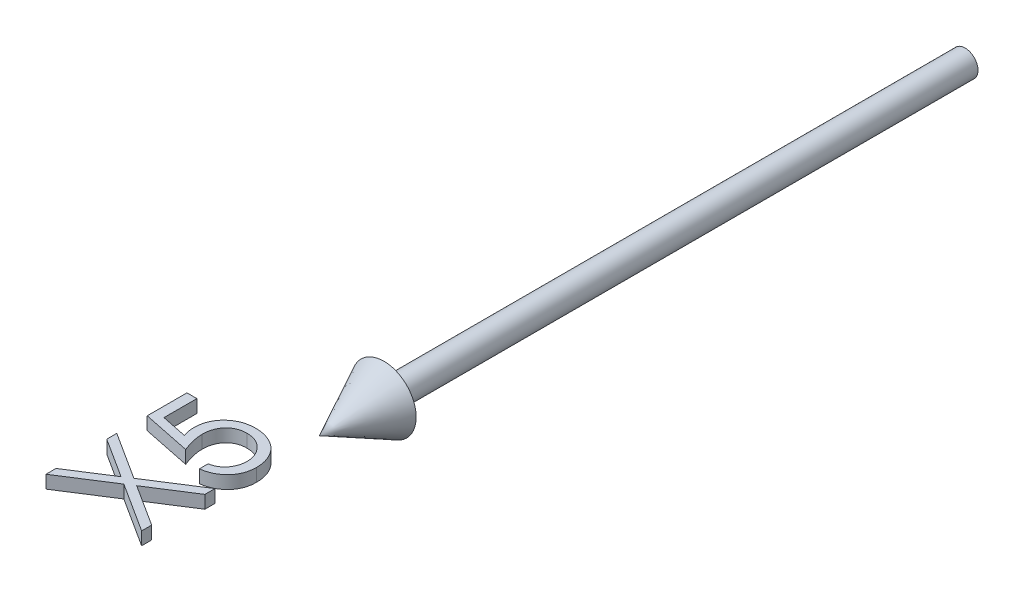
SolidWorks part; units mm, degrees
ref_plane "Front Plane" through (0, 0, 0) normal (0, 0, 1) x (1, 0, 0)
ref_plane "Top Plane" through (0, 0, 0) normal (0, 1, 0) x (1, 0, 0)
ref_plane "Right Plane" through (0, 0, 0) normal (1, 0, 0) x (0, 0, -1)
sketch "Sketch2" plane through (0, 0, 0) normal (0, 1, 0) x (1, 0, 0)
  line L0 (0, 41.95) -> (0, -114.4521) construction
  line L1 (-36.8894, 0) -> (41.4965, 0) construction
  line L2 (0, -100) -> (5, -90)
  line L3 (5, -90) -> (2, -90)
  line L4 (2, -90) -> (2, 0)
  line L5 (2, 0) -> (0, 0)
  line L6 (0, 0) -> (0, -100)
  dimension "D1" = 100
  dimension "D2" = 2
  dimension "D3" = 10
  dimension "D4" = 5
revolve "Revolve1" add sketch "Sketch2" angle 360 about L0
sketch "Sketch3" plane through (0, 0, 0) normal (0, 1, 0) x (1, 0, 0)
  line L0 (0, -103.9528) -> (0, -147.2622) construction
  line L1 (-18.6107, -118.3811) -> (18.3141, -118.3811) construction
  text T0 "X5\r\n\r\n" font "Century Gothic" height 15
extrude "Boss-Extrude1" add sketch "Sketch3" against normal blind 1 and the other way blind 1 separate body
equation "\"frame_arrow_length\"=100"
equation "\"D1@Sketch2\"=\"frame_arrow_length\""
equation "\"frame_arrow_odA\"=4"
equation "\"D2@Sketch2\"=\"frame_arrow_odA\"/2"
equation "\"frame_arrow_head_od\"=5"
equation "\"D4@Sketch2\"=\"frame_arrow_head_od\""
equation "\"frame_arrow_head_length\"=10"
equation "\"D3@Sketch2\"=\"frame_arrow_head_length\""
equation "\"tvarobot_theta1\"=30"
equation "\"link0_ringA_odA\"= 40"
equation "\"link0_ringA_odB\"= 25"
equation "\"link0_ringA_id\"= 20"
equation "\"link0_ringA_thickness\"= (\"link0_ringA_odB\" - \"link0_ringA_id\")/2"
equation "\"link0_ringA_height\"= 3"
equation "\"link0_ringA_heightA\"= 1.5"
equation "\"link0_ringA_heightB\"=\"link0_ringA_height\"-\"link0_ringA_heightA\""
equation "\"link0_ringB_odA\"= 40"
equation "\"link0_ringB_odB\"= 29"
equation "\"link0_ringB_id\"= \"link0_shaftA_bearing_id\"+1"
equation "\"link0_ringB_thickness\"= (\"link0_ringB_odB\" - \"link0_ringB_id\")/2"
equation "\"link0_ringB_height\"= 3"
equation "\"link0_ringB_heightA\"= 1.5"
equation "\"link0_ringB_heightB\"=\"link0_ringB_height\"-\"link0_ringB_heightA\""
equation "\"link0_shaftA_bearing_od\"=27"
equation "\"link0_shaftA_bearing_id\"=20"
equation "\"link0_shaftA_thrust_bearing_od\"=35"
equation "\"link0_shaftA_thrust_bearing_id\"=20.04"
equation "\"link0_shaftA_retaining_ring_id\"=18.5"
equation "\"link0_shaftA_retaining_ring_groove_width\"=1.5"
equation "\"link0_shaftA_spline_length\"=8.0"
equation "\"link0_shaftA_spline_depth\"=1.0"
equation "\"link0_shaftA_spline_width\"=4.0"
equation "\"link0_shaftA_odA\"=\"link0_shaftA_bearing_id\""
equation "\"link0_shaftA_odB\"=35"
equation "\"link0_shaftA_odC\"=\"link0_shaftA_bearing_id\""
equation "\"link0_shaftA_odD\"=\"link0_shaftA_odC\"-2*\"link0_shaftA_spline_depth\""
equation "\"link0_shaftA_odE\"=\"link0_shaftA_bearing_id\""
equation "\"link0_shaftA_odF\"=\"link0_shaftA_odE\"-2*\"link0_shaftA_spline_depth\""
equation "\"link0_shaftA_idA\"=10"
equation "\"link0_shaftA_idB\"=6"
equation "\"link0_shaftA_length\"=39.5"
equation "\"link0_shaftA_lengthA\"=8.0"
equation "\"link0_shaftA_lengthB\"=12.0"
equation "\"link0_shaftA_lengthC\"=35.0"
equation "\"link0_shaftA_lengthD\"=39.0"
equation "\"link0_shaftA_lengthE\"=\"link0_shaftA_length\"-\"link0_shaftA_lengthD\""
equation "\"link0_shaftA_offsetX\"=11"
equation "\"link0_shaftA_offsetY\"=0"
equation "\"link0_shaftA_bolt_pattern_dia\"=14"
equation "\"link0_motor_center_dist\"=26"
equation "\"link0_46t_pulley_spline_length\"=8"
equation "\"link0_46t_pulley_spline_depth\"=\"link0_shaftA_spline_depth\"*1.025"
equation "\"link0_46t_pulley_spline_width\"=\"link0_shaftA_spline_width\"*1.05"
equation "\"link0_46t_pulley_idA\"=\"link0_shaftA_bearing_id\"*1.025"
equation "\"link0_46t_pulley_idB\"=\"link0_46t_pulley_idA\"-2*\"link0_46t_pulley_spline_depth\""
equation "\"link0_shaftB_spline_length\"=10"
equation "\"link0_shaftB_spline_depth\"=1.0"
equation "\"link0_shaftB_spline_width\"=1.25"
equation "\"link0_shaftB_length\"=7"
equation "\"link0_shaftB_lengthA\"=1.5"
equation "\"link0_shaftB_lengthB\"=2.75"
equation "\"link0_shaftB_odA\"=32"
equation "\"link0_shaftB_odB\"=22"
equation "\"link0_shaftB_odC\"=20"
equation "\"link0_shaftB_idA\"=10"
equation "\"link0_shaftB_bolt_diameter\"=19"
equation "\"link0_shaftB_bearing_od\"=27"
equation "\"link0_shaftB_bearing_id\"=20"
equation "\"link0_motor_length\"=46.5"
equation "\"link0_motor_width\"=28.5"
equation "\"link0_motor_height\"=34"
equation "\"link0_motor_offset\"=8"
equation "\"link0_shellA_thickness\"=2.5"
equation "\"link0_shellB_thickness\"=\"link0_shellA_thickness\""
equation "\"link0_plateA_shellA_height\"=48"
equation "\"link0_shellA_width\" =\"link0_plateA_width\""
equation "\"link0_shellA_height\" = \"link0_plateA_shellA_height\"-\"link0_plateA_height\""
equation "\"link0_shellA_length\" = \"link0_plateA_lengthB\" "
equation "\"link0_shellB_length\"=\"link0_shellA_length\""
equation "\"link0_shellA_radius\" = 0.375*25.4"
equation "\"link0_shellA_radiusA\"= \"link0_plateA_radiusA\""
equation "\"link0_shellA_radiusB\"= \"link0_plateA_radiusB\""
equation "\"link0_shellA_radiusC\"= 3"
equation "\"link0_postA_height\"=7"
equation "\"link0_postA_width\"=16"
equation "\"link0_postA_length\"=20"
equation "\"link0_postA_posX\"=22"
equation "\"link0_postA_posY\"=17.5"
equation "\"link0_postA_pocket_width\"=6.0"
equation "\"link0_postA_pocket_length\"=2.5"
equation "\"link0_postA_pocket_depth\"=9"
equation "\"link0_postA_pocket_posZ\"=10"
equation "\"link0_postB_height\"=7"
equation "\"link0_postB_width\"=16"
equation "\"link0_postB_length\"=20"
equation "\"link0_postB_posX\"=22"
equation "\"link0_postB_posY\"=17.5"
equation "\"link0_postB_id\"=3.0"
equation "\"link0_postB_pocket_width\"=6.0"
equation "\"link0_postB_pocket_length\"=2.5"
equation "\"link0_postB_pocket_depth\"=9"
equation "\"link0_postB_pocket_posZ\"=10"
equation "\"link0_postC_height\"=7"
equation "\"link0_postC_width\"=16"
equation "\"link0_postC_length\"=20"
equation "\"link0_postC_posX\"=22"
equation "\"link0_postC_posY\"=17.5"
equation "\"link0_postC_id\"=3.0"
equation "\"link0_postC_pocket_width\"=6.0"
equation "\"link0_postC_pocket_length\"=2.5"
equation "\"link0_postC_pocket_depth\"=9"
equation "\"link0_postC_pocket_posZ\"=10"
equation "\"link0_postD_height\"=7"
equation "\"link0_postD_width\"=16"
equation "\"link0_postD_length\"=20"
equation "\"link0_postD_posX\"=22"
equation "\"link0_postD_posY\"=17.5"
equation "\"link0_postD_id\"=3.0"
equation "\"link0_postD_pocket_width\"=6.0"
equation "\"link0_postD_pocket_length\"=3.0"
equation "\"link0_postD_pocket_depth\"=9"
equation "\"link0_postD_pocket_posZ\"=10"
equation "\"link0_postE_height\"=5"
equation "\"link0_postE_width\"=16"
equation "\"link0_postE_length\"=\"link0_plateE_lengthA\"-\"link0_lip_height\""
equation "\"link0_postE_posZ\"=22"
equation "\"link0_postE_posX\"=17.5"
equation "\"link0_postE_posY\"=22"
equation "\"link0_postE_id\"=3.0"
equation "\"link0_postE_cbore_id\"=6.5"
equation "\"link0_postE_hole_id\"=3"
equation "\"link0_postF_posZ\"=22"
equation "\"link0_postF_posX\"=17.5"
equation "\"link0_postF_posY\"=\"link0_plateB_lengthA\"+4"
equation "\"link0_postF_id\"=3.0"
equation "\"link0_postF_cbore_id\"=6.5"
equation "\"link0_postF_hole_id\"=3"
equation "\"link0_postG_posZ\"=22"
equation "\"link0_postG_posX\"=17.5"
equation "\"link0_postG_posY\"=\"link0_plateB_lengthA\"+12"
equation "\"link0_postG_id\"=3.0"
equation "\"link0_postG_cbore_id\"=6.5"
equation "\"link0_postG_hole_id\"=3"
equation "\"link0_postHIJ_posY\"=6"
equation "\"link0_postH_posX\"=28"
equation "\"link0_postH_posY\"=20"
equation "\"link0_postH_posZ\"=20"
equation "\"link0_postH_length\"=10"
equation "\"link0_postI_posX\"=28"
equation "\"link0_postI_posY\"=20"
equation "\"link0_postI_posZ\"=135"
equation "\"link0_postI_length\"=10"
equation "\"link0_postJ_posX\"=28"
equation "\"link0_postJ_posY\"=20"
equation "\"link0_postJ_posZ\"=175"
equation "\"link0_postJ_length\"=10"
equation "\"link0_postK_posX\"=28"
equation "\"link0_postK_posY\"=20"
equation "\"link0_postK_posZ\"=175"
equation "\"link0_postK_length\"=10"
equation "\"link0_postL_posX\"=28"
equation "\"link0_postL_posY\"=20"
equation "\"link0_postL_posZ\"=135"
equation "\"link0_postL_length\"=10"
equation "\"link0_postM_posX\"=28"
equation "\"link0_postM_posY\"=20"
equation "\"link0_postM_posZ\"=35"
equation "\"link0_postM_length\"=10"
equation "\"link0_plateA_lengthA\"=30"
equation "\"link0_plateA_lengthB\"=150"
equation "\"link0_plateA_lengthC\"=30"
equation "\"link0_plateA_length\"=\"link0_plateA_lengthA\"+\"link0_plateA_lengthB\"+\"link0_plateA_lengthC\""
equation "\"link0_plateA_width\"=  68"
equation "\"link0_plateA_height\"= \"link0_plateA_radiusA\""
equation "\"link0_plateA_thickness\"=\"link0_shellA_thickness\""
equation "\"link0_plateA_radius\"= 9.5"
equation "\"link0_plateA_radiusA\"= 18"
equation "\"link0_plateA_radiusB\"= 18"
equation "\"link0_plateA_radiusC\"= 3"
equation "\"link0_plateB_length\"= 40"
equation "\"link0_plateB_width\"= \"link0_plateA_width\"*1.005"
equation "\"link0_plateB_height\"= \"link0_plateA_shellA_height\"*1.005"
equation "\"link0_plateB_lengthA\"=\"link0_lip_height\"+\"link0_plateD_thickness\"+\"link0_motor_mount_thickness\""
equation "\"link0_plateB_lengthB\"=\"link0_plateB_height\"-\"link0_plateB_lengthA\""
equation "\"link0_plateB_radiusA\"= \"link0_plateA_radiusA\""
equation "\"link0_plateB_radiusB\"= \"link0_plateA_radiusB\""
equation "\"link0_plateB_radiusC\"= 3"
equation "\"link0_plateB_idA\"=\"link0_shaftA_odC\"+1"
equation "\"link0_plateB_idB\"=\"link0_shaftA_bearing_od\"-2"
equation "\"link0_plateB_idC\"=\"link0_shaftA_bearing_od\"*1.005"
equation "\"link0_plateB_idD\"=\"link0_shaftA_thrust_bearing_od\"+1 "
equation "\"link0_plateB_depthA\"=1.0"
equation "\"link0_plateB_depthB\"=2.0"
equation "\"link0_plateB_depthC\"=8"
equation "\"link0_plateB_depthD\"=\"link0_plateB_length\"-\"link0_lip_height\"-\"link0_plateD_thickness\" "
equation "\"link0_plateC_length\"=\"link0_plateB_length\""
equation "\"link0_plateC_width\"= \"link0_plateB_width\""
equation "\"link0_plateC_height\"= .1*25.4"
equation "\"link0_plateA_hole_od\" = 0.1*25.4"
equation "\"link0_plateA_hole_delx\" = 0.5*25.4"
equation "\"link0_plateA_hole_delz\" = 0.75*25.4"
equation "\"link0_plateA_hole_offx\" = 0.0*25.4"
equation "\"link0_plateA_hole_offz\" = \"link0_plateA_length\"/2"
equation "\"link0_plateB_hole_od\" = 0.1*25.4"
equation "\"link0_plateB_hole_delx\"= 0.75*25.4"
equation "\"link0_plateB_hole_delz\"= 0.75*25.4"
equation "\"link0_plateB_hole_offx\"= 0.0*25.4"
equation "\"link0_plateB_hole_offz\"= 0.0*25.4"
equation "\"link0_plateC_hole_od\"= 0.1*25.4"
equation "\"link0_plateC_hole_delx\"= 0.75*25.4"
equation "\"link0_plateC_hole_delz\"= 0.75*25.4"
equation "\"link0_plateC_hole_offx\"= 0.0*25.4"
equation "\"link0_plateC_hole_offz\"= 0.0*25.4"
equation "\"link0_plateD_height\"=\"link0_plateB_height\"-2*\"link0_shellA_thickness\""
equation "\"link0_plateD_width\"=\"link0_plateB_width\"-2*\"link0_shellA_thickness\""
equation "\"link0_plateD_thickness\"=10"
equation "\"link0_plateD_radiusA\"=\"link0_plateB_radiusA\"-\"link0_shellA_thickness\""
equation "\"link0_plateD_odA\"= .375*25.4"
equation "\"link0_plateD_odB\"= .375*25.4"
equation "\"link0_plateD_bearing_id\"=20"
equation "\"link0_plateD_bearing_od\"=27"
equation "\"link0_plateE_radiusA\"=\"link0_plateA_radiusA\""
equation "\"link0_plateE_radiusB\"=\"link0_plateA_radiusB\""
equation "\"link0_plateE_radiusC\"=8.0"
equation "\"link0_plateE_length\"=30"
equation "\"link0_plateE_lengthA\"=16"
equation "\"link0_plateE_height\"=\"link0_plateB_height\""
equation "\"link0_plateE_width\"=\"link0_plateB_width\""
equation "\"link0_plateE_odA\"=\"gantry_coupler_id\"*0.99"
equation "\"link0_plateE_idA\"=\"link0_plateE_odA\"-20.0"
equation "\"link0_plateE_spline_depth\"=\"link0_poleA_spline_depth\"*1.05"
equation "\"link0_plateE_spline_width\"=\"link0_poleA_spline_width\"*1.075"
equation "\"link0_plateE_spline_length\"=\"link0_poleA_spline_length\""
equation "\"link0_plateE_coupler_length\"=46"
equation "\"link0_lip_height\"=5.0"
equation "\"link0_lip_thickness\"=2.0"
equation "\"link0_motor_mount_thickness\"=8.0"
equation "\"link0_motor_mount_idA\"=22"
equation "\"link0_motor_mount_idB\"=\"link0_shaftB_bearing_od\"*1.005"
equation "\"link0_motor_mount_idC\"=\"link0_shaftB_bearing_od\"-2"
equation "\"link0_motor_mount_depthA\"=5.5"
equation "\"link0_motor_mount_height\"=\"link0_plateD_height\""
equation "\"link0_motor_mount_width\"=\"link0_plateD_width\""
equation "\"link0_motor_mountL_height\"=36"
equation "\"link0_motor_mountL_heightA\"=12"
equation "\"link0_motor_mountL_length\"=50"
equation "\"link0_motor_mountL_lengthA\"=36"
equation "\"gantry_coupler_od\"=25.4*2.0"
equation "\"gantry_coupler_id\"=1.645*25.4"
equation "\"gantry_coupler_offsetX\"=\"link0_plateE_width\"/2"
equation "\"link0_poleA_odA\"=20"
equation "\"link0_poleA_odB\"=36"
equation "\"link0_poleA_idA\"=\"link0_poleA_odA\"-2*\"link0_poleA_thickness\""
equation "\"link0_poleA_idB\"=(\"link0_plateE_idA\"/2+1.5*\"link0_lip_thickness\")*1.04"
equation "\"link0_poleA_thickness\"=3.5"
equation "\"link0_poleA_length\"=100"
equation "\"link0_poleA_lengthA\"=18.5"
equation "\"link0_poleA_lengthB\"=80"
equation "\"link0_poleA_gasket_thickness\"=1.5"
equation "\"link0_poleA_spline_depth\"=1.0"
equation "\"link0_poleA_spline_width\"=4.0"
equation "\"link0_poleA_spline_length\"=10.0"
equation "\"link1_plateB_length\"=30"
equation "\"link1_lip_height\"=\"link0_lip_height\""
equation "\"link0_tension_plateA_width\"=12"
equation "\"link0_tension_plateA_lengthA\"=10.5"
equation "\"link0_tension_plateB_width\"=\"link0_tension_plateA_width\""
equation "\"link0_tension_plateB_lengthA\"=\"link0_tension_plateA_lengthA\""
equation "\"link0_tension_wheelA_posZ\"=7"
equation "\"link0_tension_wheelA_posX\"=\"link0_plateD_height\"/2-\"link0_tension_plateA_lengthA\""
equation "\"link0_m2_clear_hole_id\"=2.35"
equation "\"link0_m2_insert_hole_id\"=2.5"
equation "\"link0_m2_tap_hole_id\"=1.75"
equation "\"link0_m2_nut_socket_width\"=4.25"
equation "\"link0_m2_nut_socket_depth\"=2.5"
equation "\"link0_m2_cbore_id\"=3.75"
equation "\"link0_m2_cbore_depth\"=7"
equation "\"link0_m2_5_clear_hole_id\"=2.75"
equation "\"link0_m2_5_insert_hole_id\"=2.75"
equation "\"link0_m2_5_tap_hole_id\"=2.25"
equation "\"link0_m2_5_nut_socket_width\"=5.25"
equation "\"link0_m2_5_nut_socket_depth\"=2.5"
equation "\"link0_m2_5_cbore_id\"=4.75"
equation "\"link0_m2_5_cbore_depth\"=2.5"
equation "\"link0_m2_5_insert_access_length\"=6.0"
equation "\"link0_m2_5_insert_access_width\"=3.0"
equation "\"link0_m3_clear_hole_id\"=3.25"
equation "\"link0_m3_insert_hole_id\"=3"
equation "\"link0_m3_tap_hole_id\"=2.75"
equation "\"link0_m3_nut_socket_width\"=5.75"
equation "\"link0_m3_nut_socket_depth\"=4.0"
equation "\"link0_m3_cbore_id\"=5.75"
equation "\"link0_m3_cbore_depth\"=3.5"
equation "\"link0_m3_insert_access_length\"=4.5"
equation "\"link0_m3_insert_access_width\"=3.5"
equation "\"link0_rpi_mount_height\"=6"
equation "\"link0_rpi_mount_width\"=49"
equation "\"link0_rpi_mount_length\"=58"
equation "\"link0_rpi_mount_post_od\"=6"
equation "\"link0_rpi_mount_posZ\"=72"
equation "\"link0_rpi_mount_posX\"=11.5"
equation "\"link0_mcu_mount_height\"=5"
equation "\"link0_mcu_mount_width\"=49"
equation "\"link0_mcu_mount_length\"=58"
equation "\"link0_mcu_mount_post_od\"=6"
equation "\"link0_mcu_mount_posZ\"=164"
equation "\"link0_mcu_mount_posX\"=4"
equation "\"link0_pwr_mount_height\"=4"
equation "\"link0_pwr_mount_width\"=15.75"
equation "\"link0_pwr_mount_length\"=75.75"
equation "\"link0_pwr_mount_post_od\"=6"
equation "\"link0_pwr_mount_posZ\"=75"
equation "\"link0_pwr_mount_posX\"=16"
equation "\"link0_pwr_board_height\"=6"
equation "\"link0_pwr_board_width\"=21"
equation "\"link0_pwr_board_length\"=80"
